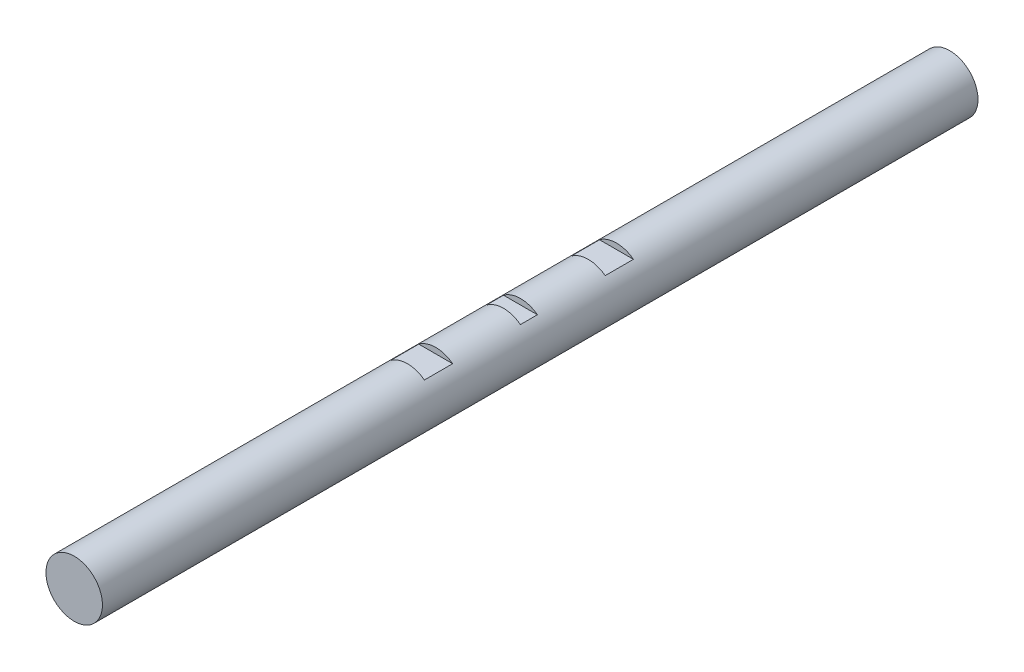
SolidWorks part; units mm, degrees
material "AISI 316 Stainless Steel Sheet (SS)"
ref_plane "Front Plane" through (0, 0, 0) normal (0, 0, 1) x (1, 0, 0)
ref_plane "Top Plane" through (0, 0, 0) normal (0, 1, 0) x (1, 0, 0)
ref_plane "Right Plane" through (0, 0, 0) normal (1, 0, 0) x (0, 0, -1)
sketch "Sketch1" plane through (0, 0, 0) normal (0, 0, 1) x (1, 0, 0)
  circle A0 centre (0, 0) radius 5
extrude "Boss-Extrude1" add sketch "Sketch1" along normal blind 77.5 and the other way blind 77.5
sketch "Sketch3" plane through (0, 0, 0) normal (1, 0, 0) x (0, 0, -1)
  line L0 (77.5, 5) -> (-77.5, 5) construction
  line L1 (18.5, 5) -> (13.5, 5)
  line L2 (18.5, 5) -> (18.5, 4)
  line L3 (18.5, 4) -> (13.5, 4)
  line L4 (13.5, 5) -> (13.5, 4)
  line L6 (-13.5, 5) -> (-18.5, 5)
  line L7 (-13.5, 5) -> (-13.5, 4)
  line L8 (-13.5, 4) -> (-18.5, 4)
  line L9 (-18.5, 5) -> (-18.5, 4)
  line L11 (1.5, 5) -> (-1.5, 5)
  line L12 (1.5, 5) -> (1.5, 4)
  line L13 (1.5, 4) -> (-1.5, 4)
  line L14 (-1.5, 5) -> (-1.5, 4)
  line L15 (77.5, 5) -> (-77.5, 5) construction
  point P8 (0, 4)
  dimension "D1" = 5
  dimension "D2" = 1
  dimension "D3" = 37
  dimension "D5" = 3
  dimension "D6" = 12
extrude "Cut-Extrude1" cut sketch "Sketch3" against normal through all both and the other way through all
